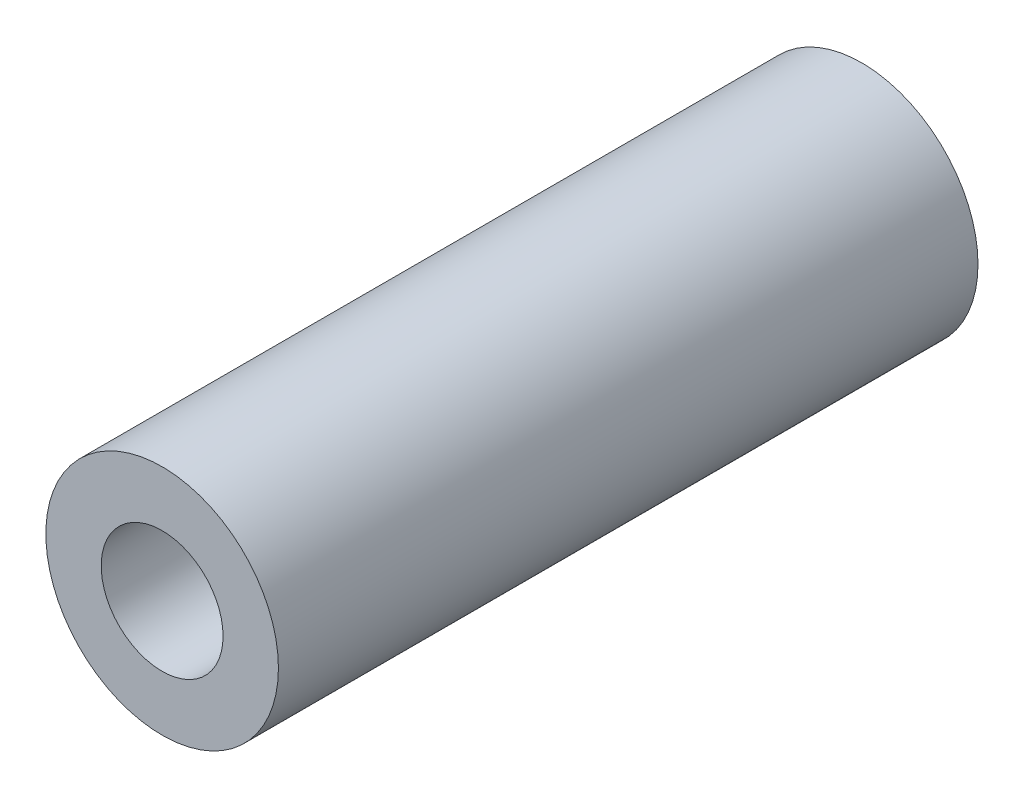
SolidWorks part; units mm, degrees
ref_plane "Front Plane" through (0, 0, 0) normal (0, 0, 1) x (1, 0, 0)
ref_plane "Top Plane" through (0, 0, 0) normal (0, 1, 0) x (1, 0, 0)
ref_plane "Right Plane" through (0, 0, 0) normal (1, 0, 0) x (0, 0, -1)
sketch "Sketch1" plane through (0, 0, 0) normal (0, 0, 1) x (1, 0, 0)
  circle A0 centre (0, 0) radius 4.7498
  circle A1 centre (0, 0) radius 2.4892
  dimension "D1" = 4.9784
  dimension "D2" = 9.4996
extrude "Boss-Extrude1" add sketch "Sketch1" along normal blind 28.575
